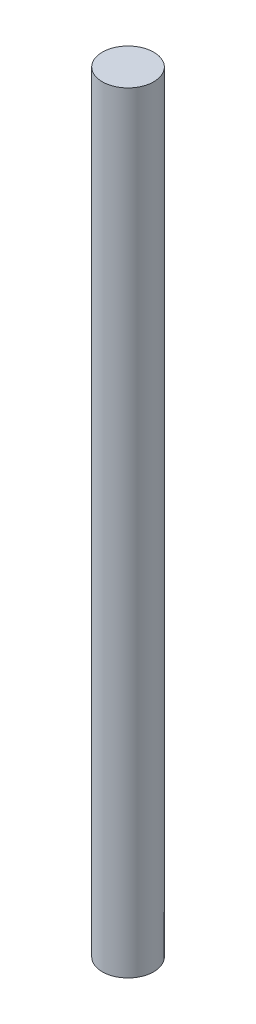
SolidWorks part; units mm, degrees
ref_plane "Спереди" through (0, 0, 0) normal (0, 0, 1) x (1, 0, 0)
ref_plane "Сверху" through (0, 0, 0) normal (0, 1, 0) x (1, 0, 0)
ref_plane "Справа" through (0, 0, 0) normal (1, 0, 0) x (0, 0, -1)
sketch "Sketch1" plane through (0, 0, 0) normal (0, 1, 0) x (1, 0, 0)
  circle A0 centre (0, 0) radius 3
  dimension "D1" = 6
extrude "Boss-Extrude1" add sketch "Sketch1" along normal blind 90
